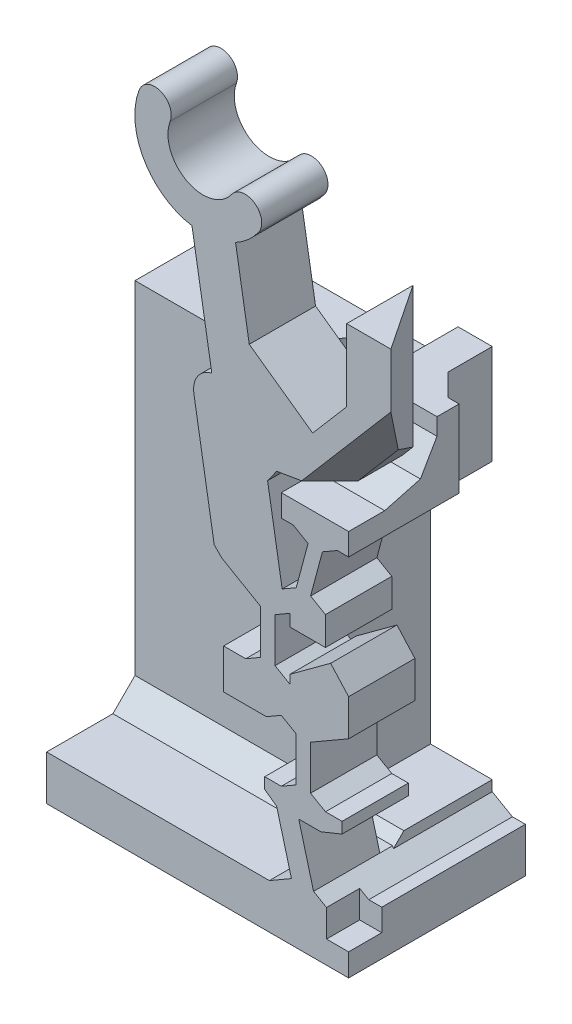
SolidWorks part; units mm, degrees
material "Nylon 6/12"
ref_plane "Front Plane" through (0, 0, 0) normal (0, 0, 1) x (1, 0, 0)
ref_plane "Top Plane" through (0, 0, 0) normal (0, 1, 0) x (1, 0, 0)
ref_plane "Right Plane" through (0, 0, 0) normal (1, 0, 0) x (0, 0, -1)
sketch "Sketch-SkeletonConfigUp" plane through (0, 0, 0) normal (0, 0, 1) x (1, 0, 0)
  line L0 (0, 0) -> (0, -50000) construction
  line L1 (0, 0) -> (4.5811, 6.2164) construction
  line L2 (9.8143, 13.3177) -> (4.5811, 13.945) construction
  line L3 (4.5811, 13.945) -> (2.9713, 10.4094) construction
  line L4 (2.9713, 10.4094) -> (4.5811, 6.2164) construction
  line L5 (4.5811, 13.945) -> (6.2429, 19.1409) construction
  line L6 (2.9713, 10.4094) -> (0.0405, 27.8193) construction
  line L7 (4.5811, 6.2164) -> (9.8143, 13.3177) construction
  line L8 (-587.3593, -797.0242) -> (9.8143, 13.3177) construction
  dimension "D2" = 7.7221
  dimension "D3" = 8.8212
  dimension "D4" = 5.2707
  dimension "D5" = 119.553
  dimension "D6" = 3.8848
  dimension "D7" = 5.4552
  dimension "D8" = 17.6549
  dimension "D9" = 4.4914
  dimension "D10" = 6.745
  dimension "D11" = 145.964
  dimension "D12" = 143.612
sketch "Sketch-SkeletonConfigDown" plane through (0, 0, 0) normal (0, 0, 1) x (1, 0, 0)
  line L0 (0, 0) -> (0, -50000) construction
  line L1 (0, 0) -> (4.5811, 6.2164) construction
  line L2 (9.8143, 13.3177) -> (4.5811, 13.945) construction
  line L3 (4.5811, 13.945) -> (6.1909, 10.4094) construction
  line L4 (6.1909, 10.4094) -> (4.5811, 6.2164) construction
  line L5 (4.5811, 13.945) -> (1.753, 18.6098) construction
  line L6 (6.1909, 10.4094) -> (-8.8652, 19.6294) construction
  line L7 (4.5811, 6.2164) -> (9.8143, 13.3177) construction
  line L8 (-589.9357, -800.5203) -> (9.8143, 13.3177) construction
  dimension "D2" = 7.7221
  dimension "D3" = 8.8212
  dimension "D4" = 5.2707
  dimension "D5" = 119.553
  dimension "D6" = 3.8848
  dimension "D7" = 5.4552
  dimension "D8" = 17.6549
  dimension "D9" = 4.4914
  dimension "D10" = 6.745
  dimension "D11" = 145.964
  dimension "D1" = 143.612
ref_plane "Plane-Cam Base" through (9.128, 0, 0) normal (1, 0, 0) x (0, 0, -1)
ref_plane "Plane-Down-to-Up Derailleur Clearance" through (6.628, 0, 0) normal (1, 0, 0) x (0, 0, -1)
ref_plane "Plane-Cam Cavity Roof" through (5.128, 0, 0) normal (1, 0, 0) x (0, 0, -1)
sketch "Sketch-SwitchBossUp" plane through (0, 0, 0) normal (0, 0, 1) x (1, 0, 0)
  line L0 (3.5811, 11.4759) -> (3.5811, 12.945) construction
  line L2 (6.5405, 21.1774) -> (6.5405, 24.4384)
  line L3 (6.5405, 24.4384) -> (8.5405, 24.4384)
  line L4 (8.5405, 24.4384) -> (8.5405, 20.4384)
  line L5 (5.5811, 12.5552) -> (5.5811, 11.263)
  line L7 (1.5115, 25.1048) -> (2.5464, 18.9575)
  line L8 (-0.4607, 24.7728) -> (0.4359, 19.4465)
  line L9 (2.9713, 10.4094) -> (0.0405, 27.8193) construction
  line L11 (-0.0396, 22.2712) -> (1.9326, 22.6032) construction
  line L15 (6.628, -55) -> (6.628, 55) construction
  line L16 (2.9713, 10.4094) -> (4.5811, 6.2164) construction
  line L17 (3.5811, 12.945) -> (3.5811, 14.945) construction
  line L18 (5.5811, 12.945) -> (5.5811, 14.945) construction
  line L19 (4.2561, 13.945) -> (4.9061, 13.945) construction
  line L20 (3.5811, 14.945) -> (5.5811, 14.945) construction
  line L21 (3.5811, 12.945) -> (5.5811, 12.945) construction
  line L22 (4.5811, 12.945) -> (4.5811, 14.945) construction
  line L23 (4.5811, 6.2164) -> (8.5405, 7.1023) construction
  line L24 (1.9713, 9.4094) -> (1.9713, 11.4094) construction
  line L25 (3.9713, 9.4094) -> (3.9713, 11.4094) construction
  line L26 (3.9713, 9.4094) -> (1.9713, 9.4094) construction
  line L27 (1.9713, 11.4094) -> (3.9713, 11.4094) construction
  line L28 (3.5811, 7.2164) -> (5.5811, 7.2164) construction
  line L29 (3.5811, 7.2164) -> (3.5811, 5.2164) construction
  line L30 (5.5811, 7.2164) -> (5.5811, 5.2164) construction
  line L31 (3.5811, 5.2164) -> (5.5811, 5.2164) construction
  line L32 (4.9061, 6.2164) -> (4.2561, 6.2164) construction
  line L40 (3.2963, 10.4094) -> (2.6463, 10.4094) construction
  line L43 (2.874, 4.5093) -> (0.7934, 4.5093) construction
  line L51 (4.9929, 19.3693) -> (2.5464, 18.9575)
  line L66 (0.0405, 27.8193) -> (0.0405, 50027.8193) construction
  line L74 (0.5455, 12.7717) -> (-0.3728, 18.2264)
  line L75 (0.3841, 13.7302) -> (2.3564, 14.0622) construction
  line L76 (5.5811, 11.263) -> (5.5811, 12.5552) construction
  line L77 (5.5811, 7.6061) -> (6.628, 8.2105)
  line L80 (5.8152, 10.763) -> (6.628, 9.8603)
  line L81 (8.5405, 1033.6218) -> (8.5405, 20.4384) construction
  line L82 (2.5464, 18.9575) -> (3.5585, 12.945) construction
  line L83 (3.6203, 12.5779) -> (2.8784, 16.9852)
  line L84 (2.8784, 16.9852) -> (6.0405, 17.5175)
  line L85 (6.9307, 9.5241) -> (8.5405, 7.7363) construction
  line L88 (3.5811, 16.3347) -> (6.8573, 16.3347)
  line L92 (3.7762, 8.3129) -> (6.9307, 9.5241) construction
  line L93 (6.3311, 4.3267) -> (5.3706, 3.937)
  line L95 (2.5464, 18.9575) -> (2.8784, 16.9852) construction
  line L96 (2.7124, 17.9713) -> (8.5405, 18.9524) construction
  line L97 (2.7124, 17.9713) -> (1.7262, 17.8053) construction
  line L98 (1.9713, 9.0197) -> (0.9713, 9.0197)
  line L99 (0.9713, 9.0197) -> (0.9713, 7.2164)
  line L100 (0.9713, 7.2164) -> (2.9061, 7.2164)
  line L101 (4.5811, 6.2164) -> (6.9307, 9.5241) construction
  line L103 (0.0405, 27.8193) -> (1.9448, 26.4638) construction
  line L104 (6.9307, 9.5241) -> (8.5405, 7.7363) construction
  line L106 (13.4416, 14.945) -> (5.5811, 14.945) construction
  line L107 (1.9713, 9.4094) -> (1.9713, 9.0197) construction
  line L109 (0.0405, 27.8193) -> (-2.1498, 28.6358) construction
  line L110 (8.5405, 20.4384) -> (6.0405, 17.5175)
  line L111 (6.628, 9.8603) -> (6.628, 8.2105)
  line L112 (6.628, 9.8603) -> (6.9307, 9.5241) construction
  line L113 (2.8311, 4.8267) -> (2.8311, 4.3267)
  line L114 (7.3693, 7.7363) -> (7.3563, 7.7363) construction
  line L115 (6.8573, 16.3347) -> (13.4416, 16.3347)
  line L116 (13.4416, 16.3347) -> (13.4416, -1.1653)
  line L117 (13.4416, -1.1653) -> (5.0405, -1.1653)
  line L119 (10.4375, 14.0252) -> (10.4375, 2.1692)
  line L121 (5.0405, -1.1653) -> (5.0405, 1.437) construction
  line L122 (8.237, 12.8031) -> (10.8393, 12.8031) construction
  line L123 (10.8393, 12.8031) -> (13.4416, 12.8031) construction
  line L124 (10.4375, 2.1692) -> (9.128, 0.8597)
  line L125 (8.5405, 7.5847) -> (13.4416, 7.5847) construction
  line L127 (5.5811, 15.3347) -> (5.5811, 14.945) construction
  line L130 (6.0405, 0.8597) -> (9.128, 0.8597)
  line L132 (2.8311, 4.3267) -> (3.3706, 3.937)
  line L133 (2.9713, 10.4094) -> (6.1909, 10.4094) construction
  line L134 (4.5811, 10.4094) -> (4.5811, 13.945) construction
  line L135 (4.5811, 10.4094) -> (4.5811, 6.2164) construction
  line L136 (0.8973, 12.4192) -> (0.5455, 12.7717)
  line L137 (3.9713, 9.4094) -> (5.5811, 7.2164) construction
  line L139 (5.8152, 10.763) -> (3.9713, 9.4094)
  line L141 (4.0405, 1.437) -> (3.0405, 0.8597)
  line L142 (3.0405, 0.8597) -> (3.0405, -1.1653)
  line L143 (8.5405, 20.4384) -> (8.5405, 18.9524) construction
  line L145 (8.5405, 17.9384) -> (8.5405, -49992.0368) construction
  line L147 (5.5811, 11.263) -> (5.5811, 12.5552) construction
  line L149 (6.3311, 4.8267) -> (6.3311, 4.3267)
  line L150 (3.0405, -1.1653) -> (5.0405, -1.1653)
  line L151 (3.3706, 3.937) -> (5.3706, 3.937) construction
  line L152 (4.792, 14.945) -> (4.2561, 12.945)
  line L153 (5.442, 14.945) -> (4.9061, 12.945)
  line L157 (3.5811, 16.3347) -> (3.5811, 15.3347)
  line L158 (6.117, 15.3347) -> (9.128, 15.3347)
  line L162 (3.2963, 11.4094) -> (3.2963, 9.4094)
  line L164 (2.6463, 11.4094) -> (2.6463, 9.4094)
  line L169 (4.2561, 7.2164) -> (4.2561, 5.2164)
  line L170 (4.9061, 5.2164) -> (4.9061, 7.2164)
  line L175 (4.2561, 7.2164) -> (3.5811, 7.6061)
  line L176 (4.9061, 7.2164) -> (5.5811, 7.6061)
  line L177 (5.5811, 7.2164) -> (5.5811, 7.6061) construction
  line L179 (4.2561, 5.2164) -> (3.5811, 4.8267)
  line L180 (3.5811, 5.2164) -> (3.5811, 4.8267) construction
  line L181 (3.5811, 4.8267) -> (2.8311, 4.8267)
  line L183 (4.9061, 5.2164) -> (5.5811, 4.8267)
  line L184 (5.5811, 5.2164) -> (5.5811, 4.8267) construction
  line L186 (9.128, -55) -> (9.128, 55) construction
  line L187 (2.6463, 9.4094) -> (1.9713, 9.0197)
  line L188 (3.2963, 9.4094) -> (3.9713, 9.0197)
  line L189 (3.2963, 11.4094) -> (3.9713, 11.7991)
  line L190 (2.6463, 11.4094) -> (0.8973, 12.4192)
  line L191 (3.9713, 11.4094) -> (3.9713, 11.7991) construction
  line L192 (3.9713, 11.7991) -> (3.9713, 11.263)
  line L193 (4.9061, 12.945) -> (5.5811, 12.5552)
  line L194 (4.2561, 12.945) -> (3.6203, 12.5779)
  line L195 (3.9713, 11.263) -> (5.5811, 11.263)
  line L196 (3.9713, 9.4094) -> (3.9713, 9.0197)
  line L197 (3.5811, 7.2164) -> (3.5811, 7.6061) construction
  line L199 (3.5811, 7.6061) -> (2.9061, 7.2164)
  line L200 (5.5811, 4.8267) -> (6.3311, 4.8267)
  line L201 (2.8311, 4.3267) -> (2.8311, 3.937) construction
  line L202 (2.8311, 3.937) -> (3.3706, 3.937) construction
  line L203 (10.4375, 14.0252) -> (9.128, 15.3347)
  line L204 (5.0405, 1.437) -> (3.0405, 1.437) construction
  line L205 (3.0405, 1.437) -> (3.0405, 0.8597) construction
  line L206 (5.0405, 1.437) -> (6.0405, 0.8597)
  line L207 (8.5405, 18.9524) -> (8.5405, 17.9384) construction
  line L208 (6.0405, 17.5175) -> (8.5405, 17.9384) construction
  line L209 (8.5405, 20.4384) -> (8.5405, 17.9384) construction
  line L210 (6.5405, 21.1774) -> (4.9929, 19.3693)
  line L211 (5.0405, 1.437) -> (4.3706, 3.937)
  line L212 (4.0405, 1.437) -> (3.3706, 3.937)
  line L213 (5.3706, 3.937) -> (4.3706, 3.937)
  line L214 (4.792, 14.945) -> (4.1169, 15.3347)
  line L215 (4.1169, 15.3347) -> (3.5811, 15.3347)
  line L216 (5.442, 14.945) -> (6.117, 15.3347)
  line L217 (5.5811, 12.945) -> (5.5811, 12.5552) construction
  line L218 (5.442, 14.945) -> (5.442, 15.3347) construction
  line L219 (6.117, 15.3347) -> (4.1169, 15.3347) construction
  arc A0 (1.5115, 25.1048) -> (2.5558, 26.0289) centre (0.0405, 27.8193) ccw
  arc A1 (-0.4607, 24.7728) -> (-2.8525, 28.8978) centre (0.0405, 27.8193) cw
  arc A2 (-2.8525, 28.8978) -> (-1.447, 28.3738) centre (-2.1498, 28.6358) cw
  arc A3 (2.5558, 26.0289) -> (1.3338, 26.8987) centre (1.9448, 26.4638) ccw
  arc A4 (-1.447, 28.3738) -> (1.3338, 26.8987) centre (0.0405, 27.8193) ccw
  arc A5 (3.5811, 12.945) -> (3.5811, 14.945) centre (3.1778, 13.945) ccw construction
  arc A6 (5.5811, 12.945) -> (5.5811, 14.945) centre (5.9843, 13.945) cw construction
  arc A7 (2.5293, 9.921) -> (1.9713, 11.4094) centre (1.568, 10.4094) ccw construction
  arc A8 (3.9713, 11.4094) -> (3.9713, 9.4094) centre (4.3745, 10.4094) ccw construction
  arc A9 (3.5811, 7.2164) -> (3.5811, 5.2164) centre (3.1779, 6.2164) cw construction
  arc A10 (5.5811, 7.2164) -> (5.5811, 5.2164) centre (5.9844, 6.2164) ccw construction
  arc A19 (-0.3728, 18.2264) -> (0.4359, 19.4465) centre (0.6836, 18.4042) cw
  circle A28 centre (0.0405, 27.8193) radius 2.3375 construction
  arc A29 (1.9713, 9.4094) -> (2.5293, 9.921) centre (1.568, 10.4094) ccw construction
  point P35 (0, 0)
  point P53 (4.5811, 13.945)
  point P63 (2.9713, 10.4094)
  point P93 (0.9465, 22.4372)
  dimension "D23" = 1.5875
  dimension "D24" = 0.75
  dimension "D2" = 2
  dimension "D5" = 2
  dimension "D6" = 0.65
  dimension "D8" = 42
  dimension "D7" = 2
  dimension "D11" = 8.5
  dimension "D14" = 7.5
  dimension "D4" = 3
  dimension "D16" = 42
  dimension "D27" = 120
  dimension "D28" = 120
  dimension "D29" = 120
  dimension "D30" = 120
  dimension "D31" = 120
  dimension "D32" = 120
  dimension "D33" = 120
  dimension "D34" = 120
  dimension "D17" = 0.5
  dimension "D20" = 3.5
  dimension "D21" = 1
  dimension "D18" = 45
  dimension "D9" = 17.5
  dimension "D22" = 1
  dimension "D15" = 45
  dimension "D38" = 2
  dimension "D39" = 0.5
  dimension "D40" = 60
  dimension "D41" = 1
  dimension "D42" = 45
  dimension "D43" = 120
  dimension "D44" = 2
  dimension "D45" = 2.5
  dimension "D46" = 2.5
  dimension "D47" = 4
  dimension "D48" = 2
  dimension "D10" = 15
  dimension "D12" = 2.5
  dimension "D13" = 1
  dimension "D19" = 1
  dimension "D25" = 15
  dimension "D26" = 120
  dimension "D35" = 120
extrude "Boss-Switch Body" add sketch "Sketch-SwitchBossUp" along normal blind 3
sketch "Sketch1" plane through (0, 0, 0) normal (0, 0, -1) x (-1, 0, 0)
  line L1 (-7.5811, -1.1653) -> (0.4122, -1.1653)
  line L2 (-7.5811, -1.1653) -> (-7.5811, 0.8597)
  line L4 (0.4122, -1.1653) -> (0.4122, 0.8597)
  line L5 (-3.5811, 18.8347) -> (-7.5811, 18.8347)
  line L10 (-7.5811, 18.8347) -> (-7.5811, 15.3347)
  line L11 (-4.0405, 1.437) -> (-5.0405, 1.437)
  line L12 (-7.5811, 15.3347) -> (-3.5811, 15.3347)
  line L13 (-4.0405, 1.437) -> (-3.0405, 0.8597)
  line L14 (-3.5811, 15.3347) -> (-3.5811, 18.8347)
  line L20 (-4.3706, 3.937) -> (-5.0405, 1.437) construction
  line L22 (-3.0405, -1.1653) -> (-13.4416, -1.1653) construction
  line L23 (-3.0405, 0.8597) -> (0.4122, 0.8597)
  line L24 (-5.0405, 1.437) -> (-6.0405, 0.8597)
  line L25 (-6.0405, 0.8597) -> (-7.5811, 0.8597)
  line L27 (-3.5811, 16.3347) -> (-3.5811, 15.3347) construction
  point P5 (-3.5811, 15.3347)
  dimension "D1" = 3.5
  dimension "D4" = 4
extrude "Boss-Flange Width" add sketch "Sketch1" along normal blind 5
ref_plane "Plane-Sta2Sit Groove" through (0.0405, 0, 0) normal (1, 0, 0) x (0, 0, -1)
ref_plane "Plane-Cam Outer Surface" through (-12.0395, 0, 0) normal (1, 0, 0) x (0, 0, -1)
ref_plane "Plane-FlangeTop" through (-7.0395, 0, 0) normal (1, 0, 0) x (0, 0, -1)
sketch "Sketch2" plane through (-7.0395, 0, 0) normal (1, 0, 0) x (0, 0, -1)
  line L0 (5, 15.3347) -> (-3, 15.3347) construction
  line L1 (5, 17.3347) -> (1, 17.3347)
  line L2 (5, 17.3347) -> (5, 15.3347)
  line L3 (5, 15.3347) -> (1, 15.3347)
  line L4 (1, 17.3347) -> (1, 15.3347)
  line L10 (-3, -1.1653) -> (-3, 16.3347) construction
  line L11 (5, 0.8597) -> (-3, 0.8597)
  line L12 (5, 0.8597) -> (5, -1.1653)
  line L13 (5, -1.1653) -> (-3, -1.1653)
  line L14 (-3, 0.8597) -> (-3, -1.1653)
  line L15 (0, 10.4094) -> (0, 27.8193) construction
  line L17 (5, 0.8597) -> (5, -1.1653) construction
  line L18 (-3, 0.8597) -> (0, 0.8597) construction
  dimension "D1" = 1
  dimension "D2" = 2
extrude "Boss-Flange Height" add sketch "Sketch2" along normal up to surface (11.6675 mm away)
sketch "Sketch10" plane through (0, 15.3347, 0) normal (0, 1, 0) x (1, 0, 0)
  line L0 (9.128, -55) -> (9.128, 55) construction
  line L1 (7.5811, 5) -> (5.128, 5)
  line L2 (7.5811, 5) -> (7.5811, 2)
  line L3 (7.5811, 2) -> (5.128, 2)
  line L5 (4.628, 7) -> (4.628, 1) construction
  line L6 (3.5811, 1) -> (-7.0395, 1) construction
  line L8 (5.128, 5) -> (5.128, 2)
  dimension "D1" = 1
  dimension "D2" = 0.5
  dimension "D3" = 4.5
extrude "Cut-Up-To-Down Derailleur Clearance" cut sketch "Sketch10" along normal up to next
sketch "Sketch17" plane through (0, 15.3347, 0) normal (0, -1, 0) x (1, 0, 0)
  line L0 (5.128, -5) -> (-7.0395, -5)
  line L1 (5.128, -5) -> (-7.0395, -5) construction
  line L2 (-7.0395, -5) -> (-7.0395, -1)
  line L3 (-7.0395, -1) -> (5.128, -1)
  line L4 (5.128, -1) -> (5.128, -5)
  line L5 (-7.0395, -1) -> (-7.0395, -5) construction
extrude "Boss-Flange Support" add sketch "Sketch17" along normal up to surface (14.475 mm away) up to face at (-1.9995, 0.8597, -1)
sketch "Sketch-HolePositions" plane through (0, -1.1653, 0) normal (0, -1, 0) x (1, 0, 0)
  line L0 (-7.0395, -3) -> (7.5811, -3) construction
  line L1 (7.5811, -5) -> (-7.0395, -5) construction
  line L2 (7.5811, -5) -> (7.5811, 0) construction
  line L4 (-7.0395, -22.2167) -> (-7.0395, 22.2167) construction
  line L5 (3.5811, -1) -> (3.5811, -5) construction
  point P6 (-4.0395, -3)
  point P7 (0.5811, -3)
  dimension "D1" = 3
  dimension "D2" = 3
  dimension "D3" = 2
sketch "Sketch6" plane through (0, -1.1653, 0) normal (0, -1, 0) x (-1, 0, 0)
  point P0 (4.0395, 3)
  point P3 (-0.5811, 3)
hole_wizard "Tap Drill for M2x0.4 Tap1" positions "Sketch6" profile "Sketch5" hole size "M2x0.4" standard "ANSI Metric" end condition through all
sketch "Sketch5" plane through (-4.0395, -1.1653, -3) normal (1, 0, 0) x (0, 0, -1)
  line L0 (0, 0) -> (0, 30.5511)
  line L1 (0, 30.5511) -> (0.8, 30.5511)
  line L2 (0.8, 30.5511) -> (0.8, 0)
  line L5 (0.8, 0) -> (0, 0)
  line L11 (0, -6.35) -> (0, 107.95) construction
  dimension "Thru Hole Dia." = 1.6
  dimension "Thru Hole Depth" = 30.5511
sketch "Sketch9" plane through (0, -1.1653, 0) normal (0, -1, 0) x (1, 0, 0)
  point P0 (-4.0395, -3)
  point P3 (0.5811, -3)
hole_wizard "M2 Clearance Hole2" positions "Sketch9" profile "Sketch8" hole size "M2" standard "ANSI Metric"
sketch "Sketch8" plane through (-4.0395, -1.1653, -3) normal (1, 0, 0) x (0, 0, -1)
  line L0 (0, 0) -> (0, 15.721)
  line L1 (0, 15.721) -> (1.2, 15)
  line L2 (1.2, 15) -> (1.2, 0)
  line L5 (1.2, 0) -> (0, 0)
  line L10 (0, 15.721) -> (-1.2, 15) construction
  line L11 (0, -6.35) -> (0, 107.95) construction
  dimension "Hole Dia." = 2.4
  dimension "Hole Depth" = 15
  dimension "Drill Angle" = 118
sketch "Sketch-Measurements for Derailleur Ramps" plane through (0, 0, 0) normal (0, 0, 1) x (1, 0, 0)
  line L0 (2.8784, 16.9852) -> (2.5464, 18.9575)
  line L1 (2.7124, 17.9713) -> (1.7262, 17.8053)
  line L2 (2.9713, 10.4094) -> (0.0405, 27.8193) construction
  line L3 (1.7262, 17.8053) -> (-1.8937, 15.3603)
  line L4 (6.1909, 10.4094) -> (-8.8652, 19.6294) construction
  line L5 (1.7262, 17.8053) -> (2.6012, 12.6077)
  line L6 (2.6012, 12.6077) -> (-1.8937, 15.3603)
  line L7 (-0.0837, 16.5828) -> (-0.0837, 17.8053)
  line L8 (-0.0837, 17.8053) -> (1.7262, 17.8053)
  line L9 (6.1909, 10.4094) -> (2.9713, 10.4094)
  line L10 (5.386, 8.3129) -> (3.7762, 8.3129)
  line L12 (6.1909, 10.4094) -> (4.5811, 6.2164) construction
  line L13 (4.5811, 8.3129) -> (4.5811, 8.7912)
  line L14 (4.5811, 6.2164) -> (5.386, 8.3129)
  line L15 (2.9713, 10.4094) -> (4.5811, 6.2164) construction
  line L16 (3.7762, 8.3129) -> (4.5811, 6.2164)
  line L17 (5.386, 8.3129) -> (5.386, 8.7912)
  dimension "D1" = 1.81
  dimension "D2" = 0.8049
sketch "Sketch12" plane through (0, 24.4384, 0) normal (0, 1, 0) x (1, 0, 0)
  line L0 (6.5405, 0) -> (8.5405, -3)
  line L1 (8.5405, -3) -> (8.5405, 0)
  line L2 (8.5405, 0) -> (6.5405, 0)
extrude "Cut-Up-to-Down Cantilever Slope" cut sketch "Sketch12" against normal up to next
ref_plane "Plane1" through (0, 7.1023, 0) normal (0, 1, 0) x (1, 0, 0)
sketch "Sketch-Derailleur Location" plane through (0, 7.1023, 0) normal (0, 1, 0) x (1, 0, 0)
  line L0 (8.5405, 0) -> (8.5405, -3)
  line L1 (4.0405, -3) -> (3.0405, -3) construction
  line L2 (-119237.4187, 0) -> (9.8143, 0) construction
  point P0 (8.5405, 0)
  point P8 (8.5405, -1.5)
ref_plane "Plane-Cantilever Cut" [suppressed] through (7.0848, 8.5204, -1.9058) normal (-0.6301, -0.7578, 0.1695) x (-0.7765, 0.6151, -0.1368)
sketch "Sketch14" [suppressed] plane through (7.0848, 8.5204, -1.9058) normal (-0.6301, -0.7578, 0.1695) x (-0.7765, 0.6151, -0.1368)
  line L0 (2.3023, -1.6911) -> (-0.3551, -1.6911)
  line L2 (2.3023, -4.3362) -> (2.3023, -1.6911)
  line L3 (-0.3551, -1.6911) -> (-0.3551, -4.4608)
  line L5 (-0.3551, -4.4608) -> (1.0087, -5.0843)
  line L6 (1.0087, -5.0843) -> (2.3023, -4.3362)
extrude "Cut-Down-to-Up Cantilever Slope" [suppressed] cut sketch "Sketch14" against normal up to next
sketch "Sketch16" plane through (0, 0, 0) normal (0, 0, -1) x (-1, 0, 0)
  line L0 (-7.5811, 18.8347) -> (-13.4416, 18.8347)
  line L1 (-13.4416, 18.8347) -> (-13.4416, -1.1653)
  line L2 (-13.4416, -1.1653) -> (-6.628, -1.1653)
  line L3 (-13.4416, -1.1653) -> (-5.0405, -1.1653) construction
  line L4 (-6.628, -1.1653) -> (-6.628, 5.2038)
  line L5 (-6.628, 5.2038) -> (-8.0037, 5.2038)
  line L6 (-8.0037, 5.2038) -> (-8.0037, 12.0484)
  line L7 (-8.0037, 12.0484) -> (-6.628, 12.0484)
  line L8 (-6.628, 12.0484) -> (-6.628, 17.9477)
  line L9 (-6.628, 55) -> (-6.628, -55) construction
  line L10 (-3.5811, 18.8347) -> (-6.5405, 18.8347) construction
  line L11 (-7.5811, 18.8347) -> (-6.628, 17.9477)
extrude "Cut-Down-to-Up Derailleur Clearance" cut sketch "Sketch16" against normal through all and the other way through all
ref_plane "Plane-Symmetry Plane" through (0, 0, 1.5) normal (0, 0, 1) x (1, 0, 0)
sketch "Sketch-Cable Center Point" plane through (0, 0, 1.5) normal (0, 0, 1) x (1, 0, 0)
  line L0 (0.0405, 27.8193) -> (0.1722, 27.0366)
  line L1 (2.9713, 10.4094) -> (0.0405, 27.8193) construction
  point P0 (0.0405, 27.8193)
  dimension "D1" = 0.7937
chamfer "Chamfer-Flange Support" distance 1.5 angle 45 1 edges at (3.5811, 17.3347, -3)
chamfer "Chamfer-Flange Support 2" distance 1 angle 45 2 edges at (5.128, 17.0847, -2) (5.128, 15.3347, -1.5)
chamfer "Chamfer-Flange Support 3" distance 1 angle 45 1 edges at (-1.9995, 0.8597, -1)
sketch "Sketch18" plane through (6.628, 0, 0) normal (1, 0, 0) x (0, 0, -1)
  line L1 (-3, -0.1403) -> (-1.5, -0.1403)
  line L2 (-3, -0.1403) -> (-3, 1.437)
  line L3 (-3, 1.437) -> (-1.5, 1.437)
  line L4 (-1.5, -0.1403) -> (-1.5, 1.437)
  line L5 (0.5774, 1.437) -> (0, 1.437) construction
  line L6 (-3, -1.1653) -> (-3, 0.8597) construction
  line L7 (-3, 0.8597) -> (5, 0.8597) construction
  dimension "D1" = 1.5
  dimension "D2" = 1
extrude "Cut-Down-to-Up Derailleur Clearance 2" cut sketch "Sketch18" against normal blind 1
sketch "Sketch19" plane through (0, 0, 0) normal (0, 0, 1) x (1, 0, 0)
  line L7 (3.5811, 18.8983) -> (6.628, 18.8983)
  line L8 (6.628, 18.8983) -> (6.628, 16.3347)
  line L9 (6.628, 16.3347) -> (3.5811, 16.3347)
  line L10 (3.5811, 16.3347) -> (3.5811, 18.8983)
  line L11 (6.628, 16.3347) -> (6.628, 17.9477) construction
  point P4 (6.628, 18.8983)
extrude "Cut-Up-to-Down Cantilever Clearance" cut sketch "Sketch19" against normal up to surface (1 mm away) up to face at (1.4435, 12.7784, -1)
chamfer "Chamfer1" distance 1 angle 60 1 edges at (5.1045, 16.3347, -1) first distance on face at (5.1045, 16.3347, 1)
chamfer "Chamfer3" distance 0.75 angle 60 1 edges at (3.5811, 16.7007, -1) first distance on face at (3.5811, 16.2811, 0.8)
chamfer "Chamfer4" distance 0.5 angle 60 1 edges at (4.205, 15.3347, -1) first distance on face at (5.0385, 15.3347, 0.5227)
chamfer "Chamfer5" distance 0.5 angle 45 1 edges at (2.8784, 16.9852, 1.5)
chamfer "Chamfer6" distance 2.5 angle 45 1 edges at (2.5464, 18.9575, 1.5)
chamfer "Chamfer7" distance 1 angle 45 1 edges at (7.2905, 18.978, 3)
sketch "Sketch22" plane through (0, 0, 0) normal (0, 0, 1) x (1, 0, 0)
  line L0 (6.628, 17.9477) -> (7.5811, 18.8347) construction
  line L1 (6.628, 18.8347) -> (7.5811, 18.8347) construction
  line L2 (6.628, 17.9477) -> (6.628, 18.8347) construction
  line L3 (6.628, 17.9477) -> (7.5811, 18.8347)
  line L4 (6.628, 18.8347) -> (7.5811, 18.8347)
  line L5 (6.628, 17.9477) -> (6.628, 18.8347)
extrude "Cut-Extrude3" cut sketch "Sketch22" against normal up to next
chamfer "Chamfer8" distance 0.5 angle 45 1 edges at (5.1045, 16.3347, 0) first distance on face at (4.2965, 17.2286, -0.5161)
sketch "Sketch23" plane through (0, 0, -1) normal (0, 0, 1) x (1, 0, 0)
  line L0 (5.128, 1.8597) -> (2.3369, 1.8597)
  line L1 (-7.0395, 1.8597) -> (5.128, 1.8597) construction
  line L2 (2.3369, 1.8597) -> (2.3369, 14.3347)
  line L3 (2.3369, 14.3347) -> (5.128, 14.3347)
  line L4 (5.128, 14.3347) -> (5.128, 1.8597)
extrude "Cut-Extrude4" cut sketch "Sketch23" against normal through all
equation "\"axle-diameter\"=2"
equation "\"switch-thickness\"=12"
equation "\"base-width\"=4.0"
equation "\"axle-bushing-radius\"=3"
equation "\"clearance\"= 0.25"
equation "\"arm-width\"=1.5"
equation "\"min-diameter\"=70"
equation "\"alpha\"=143.6120"
equation "\"gamma\"=119.5526"
equation "\"delta\"=145.9637"
equation "\"epsilon\"=6.7452"
equation "\"l_AB\"=8.8212"
equation "\"l_AC\"=4.4914"
equation "\"l_BD\"=5.2707"
equation "\"l_CD\"=3.8848"
equation "\"l_CE\"=17.6549"
equation "\"l_DF\"=5.4552"
equation "\"l_OA\"=7.7221"
equation "\"D2@Sketch-SkeletonConfigUp\" = \"l_OA\""
equation "\"D3@Sketch-SkeletonConfigUp\" = \"l_AB\""
equation "\"D4@Sketch-SkeletonConfigUp\" = \"l_BD\""
equation "\"D5@Sketch-SkeletonConfigUp\" = \"gamma\""
equation "\"D6@Sketch-SkeletonConfigUp\" = \"l_CD\""
equation "\"D7@Sketch-SkeletonConfigUp\" = \"l_DF\""
equation "\"D8@Sketch-SkeletonConfigUp\" = \"l_CE\""
equation "\"D9@Sketch-SkeletonConfigUp\" = \"l_AC\""
equation "\"D_groove\"=3.175"
equation "\"D7@Sketch-SkeletonConfigDown\" = \"l_DF\""
equation "\"D6@Sketch-SkeletonConfigDown\" = \"l_CD\""
equation "\"D2@Sketch-SkeletonConfigDown\" = \"l_OA\""
equation "\"D3@Sketch-SkeletonConfigDown\" = \"l_AB\""
equation "\"D9@Sketch-SkeletonConfigDown\" = \"l_AC\""
equation "\"D8@Sketch-SkeletonConfigDown\" = \"l_CE\""
equation "\"D5@Sketch-SkeletonConfigDown\" = \"gamma\""
equation "\"D4@Sketch-SkeletonConfigDown\" = \"l_BD\""
equation "\"D1@Sketch-SkeletonConfigDown\" = \"alpha\""
equation "\"hinge_length\"=1.5"
equation "\"hinge_depth\"=0.25"
equation "\"D10@Sketch-SkeletonConfigUp\"=\"epsilon\""
equation "\"D11@Sketch-SkeletonConfigUp\"=\"delta\""
equation "\"D12@Sketch-SkeletonConfigUp\"=\"alpha\""
equation "\"D11@Sketch-SkeletonConfigDown\"=\"delta\""
equation "\"D10@Sketch-SkeletonConfigDown\"=\"epsilon\""
equation "\"EE_dx\"=8.9056"
equation "\"EE_dy\"=8.1898"
equation "\"r_groove\"=\"D_groove\"/2"
equation "\"t_wall\"=25.4/16"
equation "\"width_lower\"=\"D_groove\"+\"t_wall\""
equation "\"cable_to_bottom\"=30.6257"
equation "\"switch_EE-up_base_dy\"=24"
equation "\"switch_EE-down_base_dy\"=16"
equation "\"D_axle\"=25.4/8"
equation "\"D_up_to_down\"=16"
equation "\"D_down_to_up\"=25"
equation "\"t_cam_base\"=7.5"
equation "\"D23@Sketch-SwitchBossUp\"=\"D_groove\"/2"
equation "\"D1@Sketch-Cable Center Point\"=\"D_groove\"/4"
